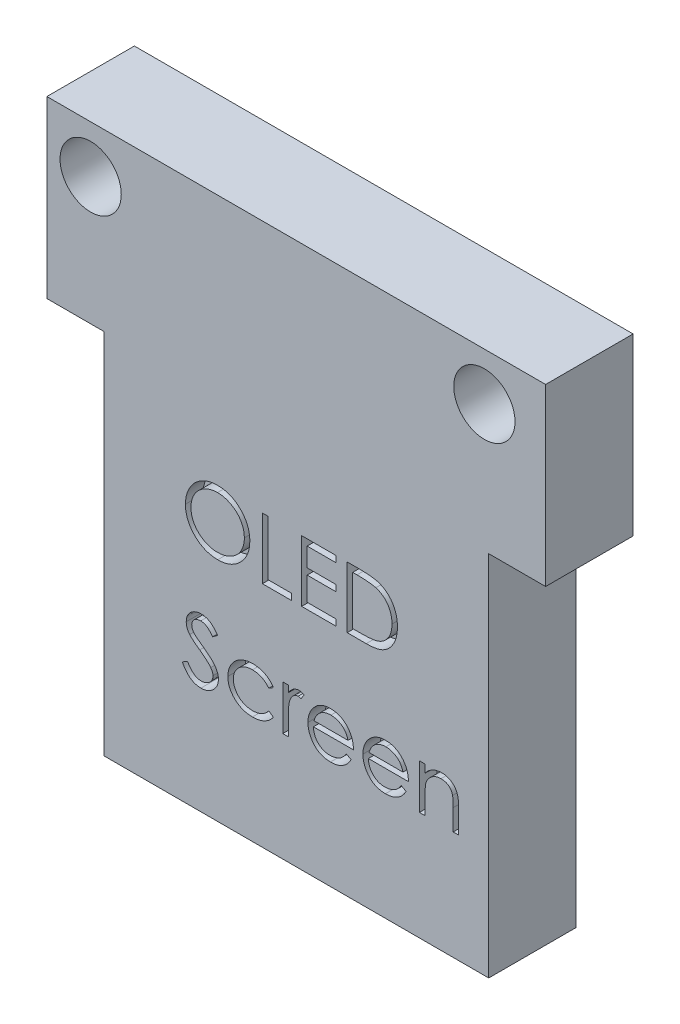
SolidWorks part; units mm, degrees
ref_plane "Front Plane" through (0, 0, 0) normal (0, 0, 1) x (1, 0, 0)
ref_plane "Top Plane" through (0, 0, 0) normal (0, 1, 0) x (1, 0, 0)
ref_plane "Right Plane" through (0, 0, 0) normal (1, 0, 0) x (0, 0, -1)
sketch "Sketch1" plane through (0, 0, 0) normal (0, 0, 1) x (1, 0, 0)
  line L1 (-14.25, 15.5) -> (14.25, 15.5)
  line L2 (-14.25, 15.5) -> (-14.25, -15.5)
  line L3 (-14.25, -15.5) -> (14.25, -15.5)
  line L4 (14.25, 15.5) -> (14.25, -15.5)
  line L5 (-14.25, 15.5) -> (14.25, -15.5) construction
  line L6 (-14.25, -15.5) -> (14.25, 15.5) construction
  line L7 (-14.25, 5.5) -> (-11, 5.5)
  line L8 (-14.25, 5.5) -> (-14.25, -15.5)
  line L9 (-14.25, -15.5) -> (-11, -15.5)
  line L10 (-11, 5.5) -> (-11, -15.5)
  line L11 (14.25, 5.5) -> (11, 5.5)
  line L12 (14.25, 5.5) -> (14.25, -15.5)
  line L13 (14.25, -15.5) -> (11, -15.5)
  line L14 (11, 5.5) -> (11, -15.5)
  circle A0 centre (-11.75, 12.7807) radius 1.75
  circle A1 centre (10.75, 12.7807) radius 1.75
  point P0 (0, 0)
  dimension "D3" = 3.5
  dimension "D4" = 3.5
  dimension "D1" = 28.5
  dimension "D2" = 31
  dimension "D5" = 22.5
  dimension "D6" = 2.5
  dimension "D7" = 3.25
  dimension "D8" = 3.25
  dimension "D9" = 21
  dimension "D10" = 21
extrude "Boss-Extrude1" add sketch "Sketch1" along normal blind 5 contours L14 L11 L4 L1 L2 L7 L10 L3 A1 A0 region at (0.0132, 0.5999, 0)
sketch "Sketch2" plane through (0, 0, 5) normal (0, 0, 1) x (1, 0, 0)
  line L0 (-6.6015, -2.4537) -> (11, -2.4537) construction
  line L3 (11, 5.5) -> (11, -15.5) construction
  text T0 "OLED\r\nScreen"
extrude "Cut-Extrude1" cut sketch "Sketch2" against normal blind 1
